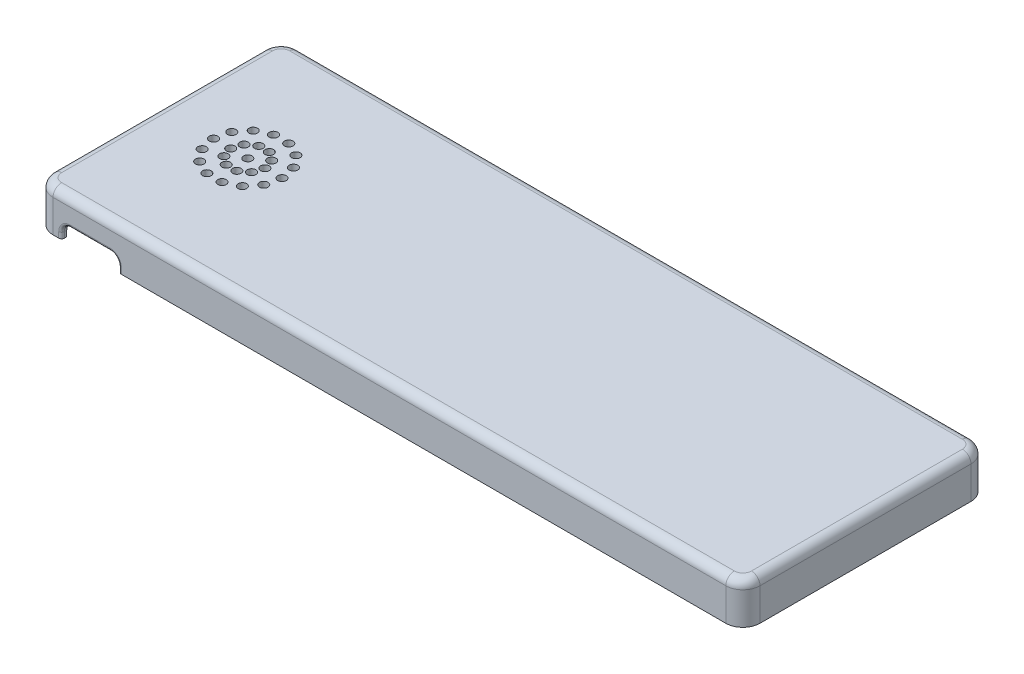
SolidWorks part; units mm, degrees
ref_plane "Спереди" through (0, 0, 0) normal (0, 0, 1) x (1, 0, 0)
ref_plane "Сверху" through (0, 0, 0) normal (0, 1, 0) x (1, 0, 0)
ref_plane "Справа" through (0, 0, 0) normal (1, 0, 0) x (0, 0, -1)
sketch "Эскиз1" plane through (0, 0, 0) normal (0, 1, 0) x (1, 0, 0)
  line L0 (62.2197, -15.4396) -> (62.2197, 21.5604) construction
  line L1 (-61.7803, 24.5604) -> (62.2197, 24.5604)
  line L2 (-61.7803, 24.5604) -> (-61.7803, -18.4396)
  line L3 (-61.7803, -18.4396) -> (62.2197, -18.4396)
  line L4 (62.2197, 24.5604) -> (62.2197, -18.4396)
  line L5 (-61.7803, 24.5604) -> (62.2197, -18.4396) construction
  line L6 (-61.7803, -18.4396) -> (62.2197, 24.5604) construction
  line L7 (59.2197, 24.5604) -> (-30.7377, 24.5604) construction
  line L8 (-58.7803, -18.4396) -> (59.2197, -18.4396) construction
  line L9 (-61.7803, 21.5604) -> (-61.7803, -15.4396) construction
  point P0 (1.4193, 3.4764)
extrude "Бобышка-Вытянуть1" add sketch "Эскиз1" along normal blind 1.2
fillet "Скругление1" radius 3 4 edges at (-61.7803, 0.6, -24.5604) (-61.7803, 0.6, 18.4396) (62.2197, 0.6, 18.4396) (62.2197, 0.6, -24.5604)
sketch "Эскиз2" plane through (0, 0, 0) normal (0, -1, 0) x (1, 0, 0)
  line L8 (-60.8803, 15.4396) -> (-60.8803, -21.5604)
  line L9 (-58.7803, -23.6604) -> (59.2197, -23.6604)
  line L10 (61.3197, -21.5604) -> (61.3197, 15.4396)
  line L11 (59.2197, 17.5396) -> (-58.7803, 17.5396)
  line L12 (-60.8803, 15.4396) -> (-60.8803, -21.5604)
  line L13 (-58.7803, -23.6604) -> (59.2197, -23.6604)
  line L14 (61.3197, -21.5604) -> (61.3197, 15.4396)
  line L15 (59.2197, 17.5396) -> (-58.7803, 17.5396)
  arc A8 (-60.8803, -21.5604) -> (-58.7803, -23.6604) centre (-58.7803, -21.5604) ccw
  arc A9 (59.2197, -23.6604) -> (61.3197, -21.5604) centre (59.2197, -21.5604) ccw
  arc A10 (61.3197, 15.4396) -> (59.2197, 17.5396) centre (59.2197, 15.4396) ccw
  arc A11 (-58.7803, 17.5396) -> (-60.8803, 15.4396) centre (-58.7803, 15.4396) ccw
  arc A12 (-60.8803, -21.5604) -> (-58.7803, -23.6604) centre (-58.7803, -21.5604) ccw
  arc A13 (59.2197, -23.6604) -> (61.3197, -21.5604) centre (59.2197, -21.5604) ccw
  arc A14 (61.3197, 15.4396) -> (59.2197, 17.5396) centre (59.2197, 15.4396) ccw
  arc A15 (-58.7803, 17.5396) -> (-60.8803, 15.4396) centre (-58.7803, 15.4396) ccw
  line M9 (-61.7803, 15.4396) -> (-61.7803, -21.5604)
  arc M10 (-61.7803, -21.5604) -> (-58.7803, -24.5604) centre (-58.7803, -21.5604) ccw
  line M11 (-58.7803, -24.5604) -> (59.2197, -24.5604)
  arc M12 (59.2197, -24.5604) -> (62.2197, -21.5604) centre (59.2197, -21.5604) ccw
  line M13 (62.2197, -21.5604) -> (62.2197, 15.4396)
  arc M14 (62.2197, 15.4396) -> (59.2197, 18.4396) centre (59.2197, 15.4396) ccw
  line M15 (59.2197, 18.4396) -> (-58.7803, 18.4396)
  arc M16 (-58.7803, 18.4396) -> (-61.7803, 15.4396) centre (-58.7803, 15.4396) ccw
  dimension "D1" = 0.9
extrude "Бобышка-Вытянуть2" add sketch "Эскиз2" along normal blind 6 contours A15 L15 A14 L14 A13 L13 A12 L12 M16 M9 M10 M11 M12 M13 M14 M15 region at (-60.8088, 0, 17.4681)
sketch "Эскиз3" plane through (0, -6, 0) normal (0, -1, 0) x (1, 0, 0)
  line L0 (-37.9803, -23.6604) -> (-37.9803, -24.5604) construction
  line L1 (-58.7803, -23.6604) -> (59.2197, -23.6604) construction
  line L2 (-58.7803, -24.5604) -> (59.2197, -24.5604) construction
  line L3 (-61.7803, 15.4396) -> (-61.7803, -21.5604) construction
  line L4 (-32.9803, -23.6604) -> (-32.9803, -24.5604)
  line L5 (-42.9803, -24.5604) -> (-42.9803, -23.6604)
  line M9 (59.2197, -23.6604) -> (-58.7803, -23.6604)
  line M15 (-58.7803, -24.5604) -> (59.2197, -24.5604)
  dimension "D1" = 23.8
  dimension "D2" = 10
extrude "Вырез-Вытянуть1" cut sketch "Эскиз3" against normal blind 3.5 contours L0 L4 M9 M15 | L0 L5 M9 M15 region at (-35.4803, -6, -24.1104) region at (-40.4803, -6, -24.1104)
fillet "Скругление2" radius 3.5 3 edges at (-37.9803, -2.5, -24.5604) (-32.9803, -4.25, -24.5604) (-42.9803, -4.25, -24.5604)
sketch "Эскиз4" plane through (0, -6, 0) normal (0, -1, 0) x (1, 0, 0)
  line L0 (-57.2803, 17.5396) -> (-57.2803, 18.4396)
  line L1 (59.2197, 17.5396) -> (-58.7803, 17.5396) construction
  line L2 (59.2197, 18.4396) -> (-58.7803, 18.4396) construction
  line L3 (-47.2803, 17.5396) -> (-47.2803, 18.4396)
  line L4 (-61.7803, 15.4396) -> (-61.7803, -21.5604) construction
  line M9 (59.2197, 18.4396) -> (-58.7803, 18.4396)
  line M19 (-58.7803, 17.5396) -> (59.2197, 17.5396)
  dimension "D1" = 4.5
  dimension "D2" = 10
extrude "Вырез-Вытянуть2" cut sketch "Эскиз4" against normal blind 2.5 contours L3 L0 M19 M9 region at (-52.2803, -6, 17.9896)
fillet "Скругление3" radius 1.5 2 edges at (-57.2803, -3.5, 17.9896) (-47.2803, -3.5, 17.9896)
fillet "Скругление4" radius 0.5 5 edges at (-47.2803, -5.5, 18.4396) (-47.7197, -3.9393, 18.4396) (-57.2803, -5.5, 18.4396) (-56.841, -3.9393, 18.4396) (-52.2803, -3.5, 18.4396)
sketch "Эскиз5" plane through (0, 1.2, 0) normal (0, 1, 0) x (1, 0, 0)
  line L0 (-61.7803, 3.0604) -> (62.2197, 3.0604) construction
  line L1 (-61.7803, 21.5604) -> (-61.7803, -15.4396) construction
  line L2 (62.2197, -15.4396) -> (62.2197, 21.5604) construction
  circle A0 centre (-46.123, 3.0604) radius 0.75
  circle A1 centre (-49.123, 3.0604) radius 0.75
  circle A2 centre (-52.123, 3.0604) radius 0.75
  circle A3 centre (-46.123, 3.0604) radius 0.75
  circle A4 centre (-49.123, 3.0604) radius 0.75
  circle A5 centre (-43.123, 3.0604) radius 0.75
  circle A6 centre (-46.123, 3.0604) radius 0.75
  circle A7 centre (-43.123, 3.0604) radius 0.75
  circle A8 centre (-40.123, 3.0604) radius 0.75
  circle A9 centre (-46.123, 3.0604) radius 0.75
  circle A12 centre (-46.123, 3.0604) radius 0.75
  circle A15 centre (-46.123, 3.0604) radius 0.75
  circle A18 centre (-46.123, 3.0604) radius 0.75
  circle A21 centre (-46.123, 3.0604) radius 0.75
  circle A24 centre (-46.123, 3.0604) radius 0.75
  circle A27 centre (-46.123, 3.0604) radius 0.75
  circle A30 centre (-46.123, 3.0604) radius 0.75
  circle A33 centre (-46.123, 3.0604) radius 0.75
  circle A36 centre (-46.123, 3.0604) radius 0.75
  circle A39 centre (-46.123, 3.0604) radius 0.75
  circle A42 centre (-46.123, 3.0604) radius 0.75
  circle A45 centre (-47.05, 5.9136) radius 0.75
  circle A46 centre (-45.1959, 0.2072) radius 0.75
  circle A47 centre (-43.6959, 4.8238) radius 0.75
  circle A48 centre (-48.55, 1.297) radius 0.75
  circle A49 centre (-43.6959, 1.297) radius 0.75
  circle A50 centre (-48.55, 4.8238) radius 0.75
  circle A51 centre (-47.05, 0.2072) radius 0.75
  circle A52 centre (-45.1959, 5.9136) radius 0.75
  circle A53 centre (-49.8639, 7.7514) radius 0.75
  circle A54 centre (-42.382, -1.6306) radius 0.75
  circle A55 centre (-44.7878, 8.91) radius 0.75
  circle A56 centre (-47.4581, -2.7892) radius 0.75
  circle A57 centre (-40.7171, 5.6637) radius 0.75
  circle A58 centre (-51.5288, 0.4571) radius 0.75
  circle A59 centre (-40.7171, 0.4571) radius 0.75
  circle A60 centre (-51.5288, 5.6637) radius 0.75
  circle A61 centre (-44.7878, -2.7892) radius 0.75
  circle A62 centre (-47.4581, 8.91) radius 0.75
  circle A63 centre (-49.8639, -1.6306) radius 0.75
  circle A64 centre (-42.382, 7.7514) radius 0.75
  point P48 (-46.123, 3.0604)
  point P79 (-46.123, 3.0604)
  point P87 (-46.123, 3.0604)
  dimension "D1" = 5
  dimension "D2" = 7
fillet "Скругление5" radius 1.5 8 edges at (-60.9016, 1.2, 17.5609) (-61.7803, 1.2, -3.0604) (-60.9016, 1.2, -23.6817) (0.2197, 1.2, -24.5604) (61.341, 1.2, -23.6817) (62.2197, 1.2, -3.0604) (61.341, 1.2, 17.5609) (0.2197, 1.2, 18.4396)
fillet "Скругление6" radius 0.8 8 edges at (60.7046, 0, 16.9245) (61.3197, 0, -3.0604) (60.7046, 0, -23.0453) (0.2197, 0, -23.6604) (-60.2652, 0, -23.0453) (-60.8803, 0, -3.0604) (-60.2652, 0, 16.9245) (0.2197, 0, 17.5396)
extrude "Вырез-Вытянуть4" cut sketch "Эскиз5" against normal up to next (1.2 mm away) contours L0 A2 | A2 L0 | L0 A4 | A1 L0 | L0 A42 | A0 L0 | L0 A7 | A5 L0 | L0 A8 | A8 L0 | A47 | A52 | A45 | A50 | A60 | A53 | A62 | A55 | A64 | A57 | A59 | A54 | A61 | A56 | A58 | A48 | A49 | A63 | A51 | A46 region at (-52.123, 1.2, -3.3787) region at (-40.123, 1.2, -3.3787) region at (-40.123, 1.2, -2.7421) region at (-43.123, 1.2, -3.3787) region at (-43.123, 1.2, -2.7421) region at (-46.123, 1.2, -3.3787) region at (-46.123, 1.2, -2.7421) region at (-49.123, 1.2, -3.3787) region at (-49.123, 1.2, -2.7421) region at (-52.123, 1.2, -2.7421) region at (-47.05, 1.2, -5.9136) region at (-45.1959, 1.2, -0.2072) region at (-43.6959, 1.2, -4.8238) region at (-48.55, 1.2, -1.297) region at (-43.6959, 1.2, -1.297) region at (-48.55, 1.2, -4.8238) region at (-47.05, 1.2, -0.2072) region at (-45.1959, 1.2, -5.9136) region at (-49.8639, 1.2, -7.7514) region at (-42.382, 1.2, 1.6306) region at (-44.7878, 1.2, -8.91) region at (-47.4581, 1.2, 2.7892) region at (-40.7171, 1.2, -5.6637) region at (-51.5288, 1.2, -0.4571) region at (-40.7171, 1.2, -0.4571) region at (-51.5288, 1.2, -5.6637) region at (-44.7878, 1.2, 2.7892) region at (-47.4581, 1.2, -8.91) region at (-49.8639, 1.2, 1.6306) region at (-42.382, 1.2, -7.7514)
